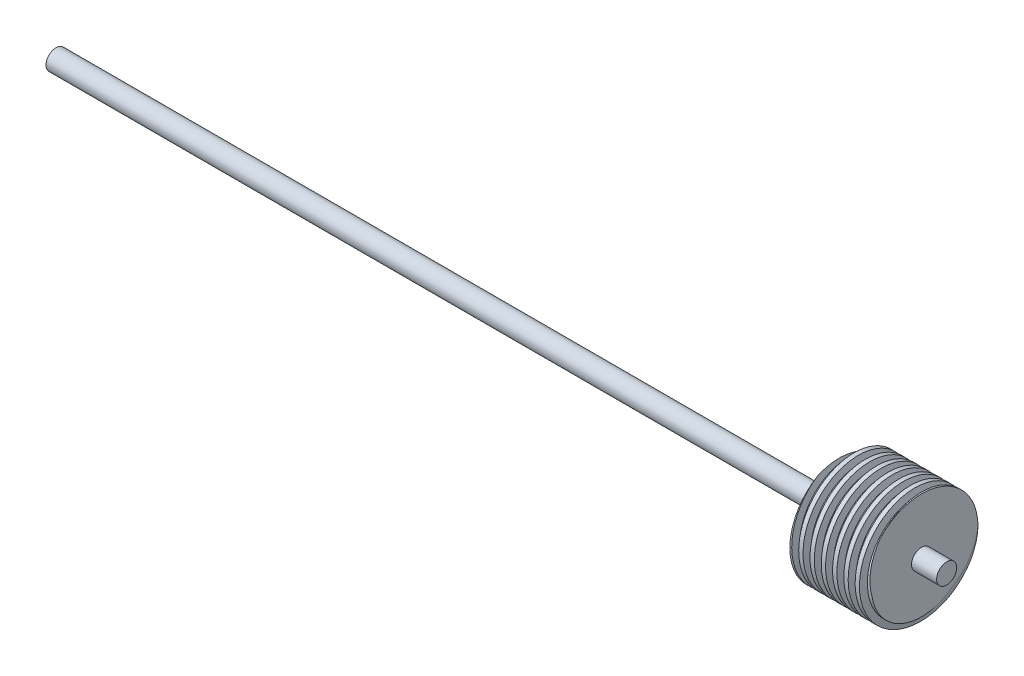
SolidWorks part; units mm, degrees
ref_plane "Front Plane" through (0, 0, 0) normal (0, 0, 1) x (1, 0, 0)
ref_plane "Top Plane" through (0, 0, 0) normal (0, 1, 0) x (1, 0, 0)
ref_plane "Right Plane" through (0, 0, 0) normal (1, 0, 0) x (0, 0, -1)
sketch "Sketch1" plane through (0, 0, 0) normal (1, 0, 0) x (0, 0, -1)
  circle A0 centre (0, 0) radius 22.5
  dimension "D1" = 45
extrude "Boss-Extrude1" add sketch "Sketch1" along normal blind 30
thread "Thread1" [suppressed] pitch 4.5 start angle 0, offset 11, length 50, pitch 4.5, diameter 45
ref_plane "Plane1" through (41, 0, 22.5) normal (0, -1, 0) x (0, 0, 1)
sketch "Thread Profile1" [suppressed] plane through (41, 0, 22.5) normal (0, -1, 0) x (0, 0, 1)
  line L0 (0, 0) -> (0, 4.5) construction
  line L11 (0, 0) -> (0, 3.9375)
  line L12 (0, 3.9375) -> (-2.4357, 2.5312)
  line L13 (-2.4357, 2.5312) -> (-2.4357, 1.4062)
  line L15 (-2.4357, 1.4062) -> (0, 0)
  line L17 (-2.4357, 1.9687) -> (0, 1.9687) construction
  point P2 (0, 0)
  dimension "Pitch" = 4.5
  dimension "Profile_Angle" = 60
  dimension "Profile_Land" = 1.125
  dimension "Profile_Height" = 2.4357
sketch "Sketch2" plane through (30, 0, 0) normal (1, 0, 0) x (0, 0, -1)
  circle A0 centre (0, 0) radius 22.5 construction
  circle A1 centre (0, 0) radius 22.5
curve "Helix/Spiral1" pitch 4.5 height 64.5 radius 22.5 centre (30, 0, 0) axis (-1, 0, 0) start towards (0, 0, -1)
sketch "Sketch3" plane through (0, 0, 0) normal (0, 1, 0) x (1, 0, 0)
  line L0 (30, 22.5) -> (32.7931, 22.5)
  line L1 (32.7931, 22.5) -> (32.1465, 20)
  line L2 (32.1465, 20) -> (30.6465, 20)
  line L3 (30.6465, 20) -> (30, 22.5)
  line L4 (31.3965, 20) -> (31.3965, 24.8246) construction
  point P3 (31.3965, 22.5)
  dimension "D1" = 29
  dimension "D2" = 2.5
  dimension "D3" = 1.5
sweep "Cut-Sweep1" cut profiles "Sketch3" path "Helix/Spiral1" align with end faces yes
sketch "Sketch4" plane through (0, 0, 0) normal (-1, 0, 0) x (0, 0, 1)
  circle A0 centre (0, 0) radius 4
  dimension "D1" = 8
extrude "Boss-Extrude2" add sketch "Sketch4" along normal blind 315 and the other way blind 40
